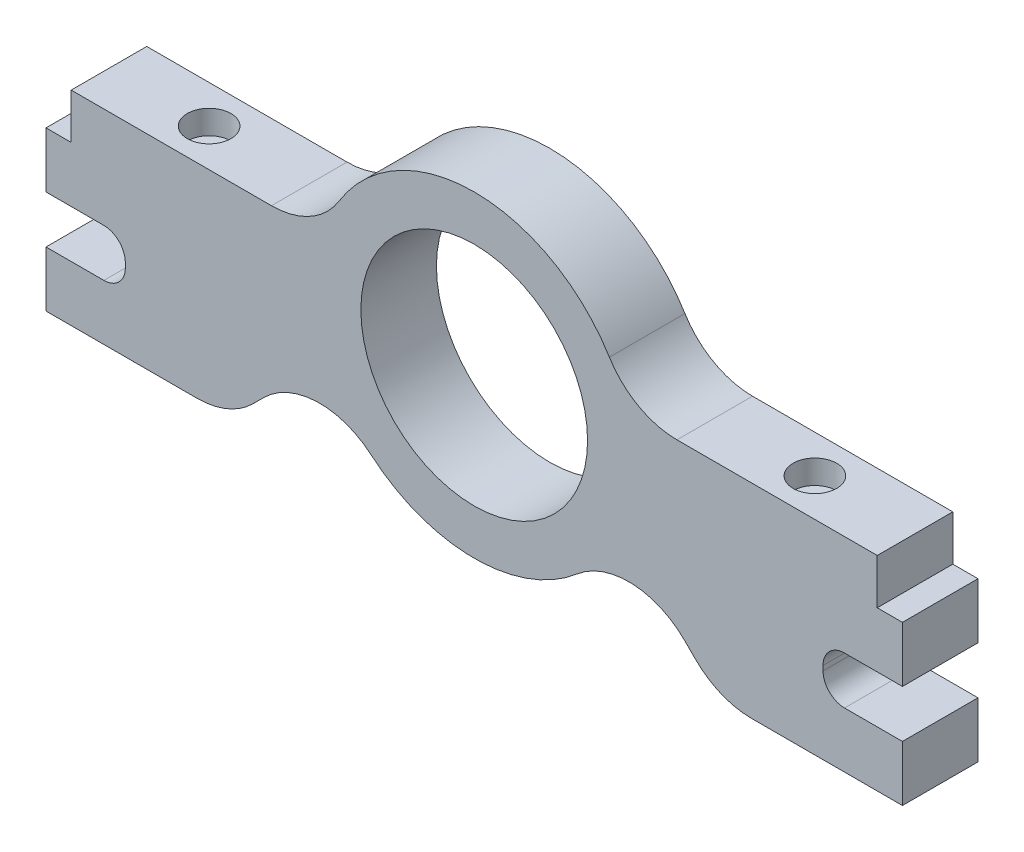
SolidWorks part; units mm, degrees
ref_plane "Front Plane" through (0, 0, 0) normal (0, 0, 1) x (1, 0, 0)
ref_plane "Top Plane" through (0, 0, 0) normal (0, 1, 0) x (1, 0, 0)
ref_plane "Right Plane" through (0, 0, 0) normal (1, 0, 0) x (0, 0, -1)
sketch "Sketch1" plane through (0, 0, 0) normal (0, 0, 1) x (1, 0, 0)
  line L0 (-14.2875, 0) -> (-50.8, 0)
  line L1 (-50.8, 0) -> (-50.8, -20)
  line L2 (50.8, -20) -> (50.8, 0)
  line L3 (50.8, 0) -> (14.2875, 0)
  line L4 (-50.8, 0) -> (-50.8, 5.7125)
  line L5 (-50.8, 5.7125) -> (-19.1668, 5.7125)
  line L6 (50.8, 0) -> (50.8, 5.7125)
  line L7 (50.8, 5.7125) -> (19.1668, 5.7125)
  line L8 (-18.4859, -7.6336) -> (-30.8, -20)
  line L9 (-30.8, -20) -> (-50.8, -20)
  line L10 (18.4859, -7.6336) -> (30.8, -20)
  line L11 (30.8, -20) -> (50.8, -20)
  circle A0 centre (0, 0) radius 14.2875
  arc A1 (-18.4859, -7.6336) -> (18.4859, -7.6336) centre (0, 0) ccw
  arc A2 (19.1668, 5.7125) -> (-19.1668, 5.7125) centre (0, 0) ccw
  dimension "D1" = 28.575
  dimension "D2" = 20
  dimension "D3" = 101.6
  dimension "D4" = 5.7125
  dimension "D5" = 20
  dimension "D6" = 20
  dimension "D7" = 0
  dimension "D8" = 20
extrude "Boss-Extrude1" add sketch "Sketch1" along normal blind 9.525 contours L8 A1 L10 L11 L2 L3 A0 L0 L1 L9 | L7 A2 L5 L4 L0 A0 L3 L6 region at (0, -15.323, 0) region at (-32.5438, 1.0355, 0)
sketch "Sketch2" plane through (50.8, 0, 0) normal (1, 0, 0) x (0, 0, -1)
  line L0 (-9.525, -20) -> (0, -20)
  line L1 (0, -20) -> (0, 0)
  line L2 (0, 0) -> (-9.525, 0)
  line L3 (-9.525, -20) -> (-9.525, 5.7125) construction
  line L4 (-9.525, 0) -> (-9.525, -20)
extrude "Boss-Extrude3" add sketch "Sketch2" along normal blind 3.175
mirror "Mirror1" about plane through (0, 0, 0) normal (1, 0, 0) of "Boss-Extrude3"
fillet "Fillet1" radius 10 4 edges at (-19.1668, 5.7125, 4.7625) (19.1668, 5.7125, 4.7625) (18.4859, -7.6336, 4.7625) (-18.4859, -7.6336, 4.7625)
fillet "Fillet2" radius 10 2 edges at (-30.8, -20, 4.7625) (30.8, -20, 4.7625)
sketch "Sketch3" plane through (0, 5.7125, 0) normal (0, 1, 0) x (1, 0, 0)
  line L0 (-50.8, -9.525) -> (-25.5562, 0)
  line L1 (-50.8, 0) -> (-25.5562, -9.525)
  circle A0 centre (-38.1781, -4.7625) radius 2.75
  circle A1 centre (-38.1781, -4.7625) radius 1.5
extrude "Cut-Extrude1" cut sketch "Sketch3" against normal blind 3 contours A1 L1 A0 L0 | A1 L0 A0 L1 | A1 L1 A0 L0 | A1 L0 A0 L1 region at (-40.3172, 5.7125, 4.7625) region at (-38.1781, 5.7125, 6.453) region at (-38.1781, 5.7125, 3.072) region at (-36.0389, 5.7125, 4.7625)
extrude "Cut-Extrude2" cut sketch "Sketch3<4>" against normal through all contours L0 A1 L1 | L1 A1 L0 | L0 A1 L1 | L1 A1 L0 region at (-39.1565, 5.7125, 4.7625) region at (-38.1781, 5.7125, 5.5357) region at (-38.1781, 5.7125, 3.9893) region at (-37.1996, 5.7125, 4.7625)
sketch "Sketch3<4>" plane through (0, 5.7125, 0) normal (0, 1, 0) x (1, 0, 0) same geometry as "Sketch3"
mirror "Mirror2" about plane through (0, 0, 0) normal (1, 0, 0) of "Cut-Extrude1", "Cut-Extrude2"
sketch "Sketch4" plane through (53.975, 0, 0) normal (1, 0, 0) x (0, 0, -1)
  line L0 (-9.525, -7) -> (0, -7)
  line L1 (-9.525, 0) -> (-9.525, -20) construction
  line L2 (0, -20) -> (0, 0) construction
  line L3 (-9.525, -13) -> (0, -13)
  line L4 (0, 0) -> (-9.525, 0) construction
  line L5 (-9.525, -20) -> (0, -20) construction
  line L6 (0, -7) -> (0, -13)
  line L7 (-9.525, -7) -> (-9.525, -13)
  dimension "D1" = 7
  dimension "D2" = 7
extrude "Cut-Extrude3" cut sketch "Sketch4" against normal blind 10
mirror "Mirror3" about plane through (0, 0, 0) normal (1, 0, 0) of "Cut-Extrude3"
fillet "Fillet3" radius 2.7 4 edges at (43.975, -13, 4.7625) (43.975, -7, 4.7625) (-43.975, -13, 4.7625) (-43.975, -7, 4.7625)
